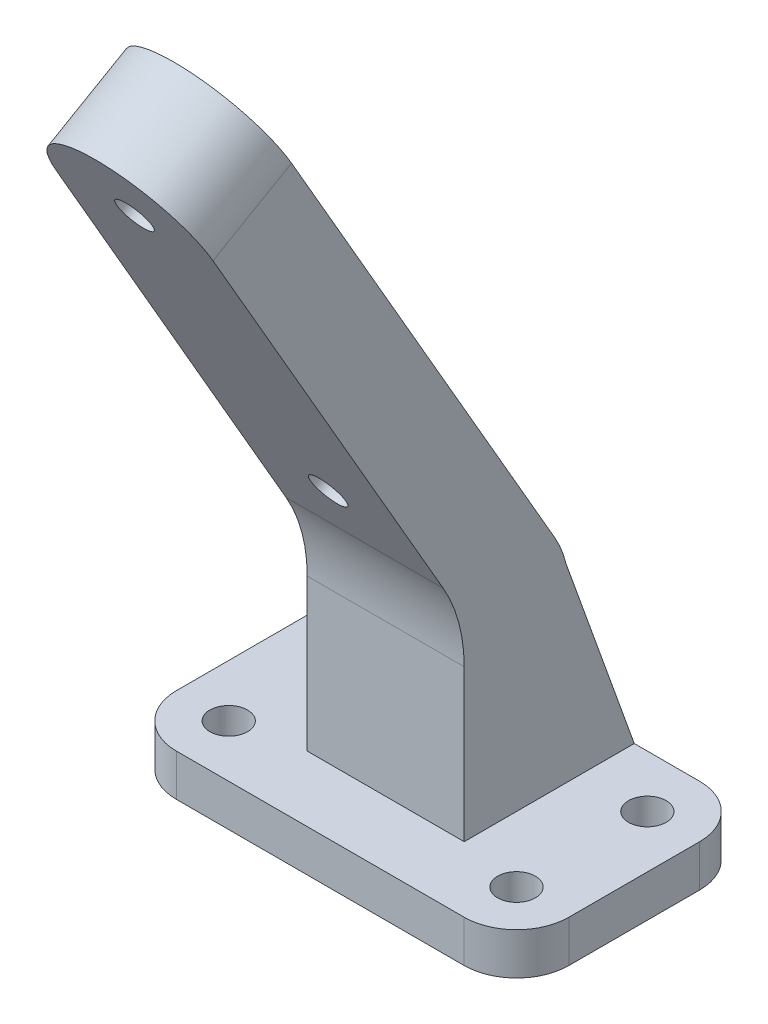
SolidWorks part; units mm, degrees
ref_plane "前视基准面" through (0, 0, 0) normal (0, 0, 1) x (1, 0, 0)
ref_plane "上视基准面" through (0, 0, 0) normal (0, 1, 0) x (1, 0, 0)
ref_plane "右视基准面" through (0, 0, 0) normal (1, 0, 0) x (0, 0, -1)
sketch "草图1" plane through (0, 0, 0) normal (0, 1, 0) x (1, 0, 0)
  line L1 (0, 0) -> (37.5, 0)
  line L2 (0, 0) -> (0, 22.5)
  line L3 (0, 22.5) -> (37.5, 22.5)
  line L4 (37.5, 0) -> (37.5, 22.5)
  dimension "D1" = 37.5
  dimension "D2" = 22.5
extrude "凸台-拉伸2" add sketch "草图1" along normal blind 4
sketch "草图2" plane through (0, 4, 0) normal (0, 1, 0) x (1, 0, 0)
  line L0 (37.5, 22.5) -> (0, 22.5) construction
  line L1 (11.25, 16.25) -> (26.25, 16.25)
  line L2 (11.25, 16.25) -> (11.25, 6.25)
  line L3 (11.25, 6.25) -> (26.25, 6.25)
  line L4 (26.25, 16.25) -> (26.25, 6.25)
  line L5 (37.5, 0) -> (37.5, 22.5) construction
  dimension "D1" = 15
  dimension "D2" = 10
  dimension "D3" = 6.25
  dimension "D4" = 11.25
extrude "凸台-拉伸3" add sketch "草图2" along normal blind 18.5
sketch "草图3" plane through (26.25, 0, 0) normal (1, 0, 0) x (0, 0, -1)
  line L0 (6.25, 22.5) -> (-17.75, 64.0692)
  line L1 (-17.75, 64.0692) -> (-10.25, 68.3993)
  line L2 (16.25, 22.5) -> (-10.25, 68.3993)
  line L3 (6.25, 22.5) -> (16.25, 22.5)
  dimension "D1" = 120
  dimension "D2" = 48
extrude "凸台-拉伸4" add sketch "草图3" against normal blind 15
sketch "草图4" plane through (0, 8.3313, -14.4303) normal (0, -0.5, 0.866) x (1, 0, 0)
  line L0 (11.25, 64.3606) -> (26.25, 64.3606) construction
  line L1 (26.25, 64.3606) -> (11.25, 64.3606)
  arc A0 (26.25, 64.3606) -> (11.25, 64.3606) centre (18.75, 64.3606) ccw
extrude "凸台-拉伸5" add sketch "草图4" against normal blind 8.6603
sketch "草图5" plane through (0, 8.3313, -14.4303) normal (0, -0.5, 0.866) x (1, 0, 0)
  line L0 (18.75, 89.0486) -> (18.75, 40.3757) construction
  circle A0 centre (18.75, 64.3606) radius 1.7
  circle A1 centre (18.75, 27.3606) radius 1.7
  dimension "D1" = 37
extrude "切除-拉伸1" cut sketch "草图5" against normal blind 10
fillet "圆角1" radius 15 1 edges at (18.75, 22.5, -6.25)
sketch "草图6" plane through (0, 0, -16.25) normal (0, 0, -1) x (-1, 0, 0)
  line L0 (-11.25, 22.5) -> (-11.25, 4) construction
  line L1 (-26.25, 22.5) -> (-11.25, 22.5)
  line L2 (-26.25, 22.5) -> (-26.25, 16.5)
  line L3 (-26.25, 16.5) -> (-11.25, 16.5)
  line L4 (-11.25, 22.5) -> (-11.25, 16.5)
  line L5 (-26.25, 22.5) -> (-26.25, 4) construction
  line L7 (-26.25, -11.5) -> (-26.25, 14)
  line L9 (-11.25, 20) -> (-11.25, 14)
  dimension "D1" = 6
  dimension "D2" = 6
  dimension "D3" = 28
ref_plane "基准面1" through (18.75, 0, 0) normal (1, 0, 0) x (0, 0, -1)
fillet "圆角3" radius 5 4 edges at (37.5, 2, 0) (37.5, 2, -22.5) (0, 2, 0) (0, 2, -22.5)
sketch "草图9" plane through (0, 4, 0) normal (0, 1, 0) x (1, 0, 0)
  line L0 (-4.692, 11.25) -> (43.8316, 11.25) construction
  line L1 (18.75, 35.0512) -> (18.75, -7.7941) construction
  line L2 (18.75, -41.5294) -> (18.75, 41.5294) construction
  line L3 (0, 17.5) -> (0, 5) construction
  line L4 (18.75, 27.2713) -> (18.75, -4.1141) construction
  circle A0 centre (5, 17.5) radius 1.8
  circle A1 centre (32.5, 17.5) radius 1.8
  circle A2 centre (32.5, 5) radius 1.8
  circle A3 centre (5, 5) radius 1.8
  point P17 (0, 11.25)
extrude "切除-拉伸2" cut sketch "草图9" against normal blind 4
fillet "圆角5" radius 10 1 edges at (18.75, 22.5, -16.25)
sketch "草图16" plane through (26.25, 0, 0) normal (1, 0, 0) x (0, 0, -1)
  line L0 (22.5, 4) -> (15.9728, 22.1589)
  arc A0 (16.25, 19.8205) -> (14.9103, 24.8205) centre (6.25, 19.8205) ccw construction
rib "筋10" sketch "草图16" sketch "草图16" thickness 4 extrusion direction parallel to sketch draft on no parameters "D1"=4
sketch "草图17" plane through (11.25, 0, 0) normal (-1, 0, 0) x (0, 0, 1)
  line L0 (-22.5, 4) -> (-15.9848, 22.1083)
  arc A0 (-14.9103, 24.8205) -> (-16.25, 19.8205) centre (-6.25, 19.8205) ccw construction
rib "筋11" sketch "草图17" sketch "草图17" thickness 4 extrusion direction parallel to sketch draft on no parameters "D1"=4
